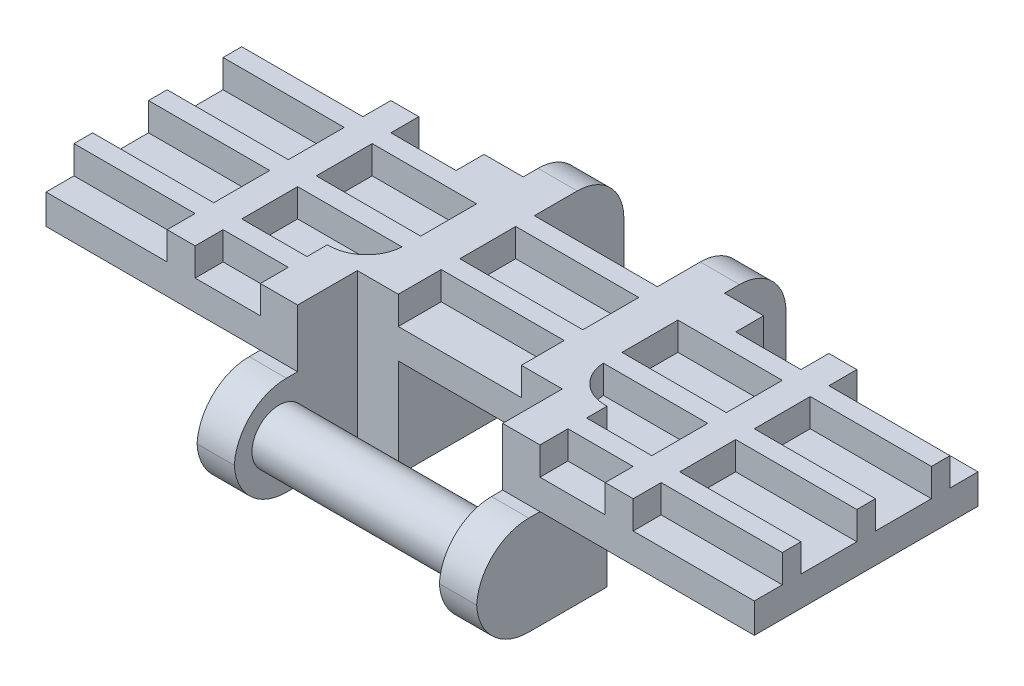
SolidWorks part; units mm, degrees
ref_plane "前视基准面" through (0, 0, 0) normal (0, 0, 1) x (1, 0, 0)
ref_plane "上视基准面" through (0, 0, 0) normal (0, 1, 0) x (1, 0, 0)
ref_plane "右视基准面" through (0, 0, 0) normal (1, 0, 0) x (0, 0, -1)
other "Configuration Table"
sketch "草图1" plane through (0, 0, 0) normal (0, 1, 0) x (1, 0, 0)
  line L1 (-19, -6) -> (19, -6)
  line L2 (-19, -6) -> (-19, 6)
  line L3 (-19, 6) -> (19, 6)
  line L4 (19, -6) -> (19, 6)
  line L5 (-19, -6) -> (19, 6) construction
  line L6 (-19, 6) -> (19, -6) construction
  line L13 (-19, 4.5) -> (19, 4.5)
  line L14 (-19, 4.5) -> (-19, 3.5)
  line L15 (-19, 3.5) -> (19, 3.5)
  line L16 (19, 4.5) -> (19, 3.5)
  line L17 (-19, 0.5) -> (19, 0.5)
  line L18 (-19, 0.5) -> (-19, -0.5)
  line L19 (-19, -0.5) -> (19, -0.5)
  line L20 (19, 0.5) -> (19, -0.5)
  line L21 (-19, -3.5) -> (19, -3.5)
  line L22 (-19, -3.5) -> (-19, -4.5)
  line L23 (-19, -4.5) -> (19, -4.5)
  line L24 (19, -3.5) -> (19, -4.5)
  line L25 (-12.5, 6) -> (-11, 6)
  line L26 (-12.5, 6) -> (-12.5, -6)
  line L27 (-12.5, -6) -> (-11, -6)
  line L28 (-11, 6) -> (-11, -6)
  line L29 (12.5, 6) -> (11, 6)
  line L30 (12.5, 6) -> (12.5, -6)
  line L31 (12.5, -6) -> (11, -6)
  line L32 (11, 6) -> (11, -6)
  point P0 (0, 0)
  point P6 (0, 0)
  dimension "D1" = 38
  dimension "D2" = 12
  dimension "D3" = 11
  dimension "D4" = 11
  dimension "D5" = 1
  dimension "D6" = 1.5
  dimension "D7" = 1.5
  dimension "D8" = 5.5
  dimension "D9" = 1.5
extrude "凸台-拉伸1" add sketch "草图1" along normal blind 1.6 contours L2 L3 L4 L1
extrude "凸台-拉伸2" add sketch "草图1<3>" along normal blind 1.5 from surface contours L13 L16 L15 L14 | L17 L20 L19 L18 | L21 L24 L23 L22 | L26 L27 L28 L25 | L30 L31 L32 L29 starting at face at (0, 1.6, 0)
sketch "草图1<3>" plane through (0, 0, 0) normal (0, 1, 0) x (1, 0, 0) same geometry as "草图1"
sketch "草图2" plane through (0, 0, 0) normal (0, 1, 0) x (1, 0, 0)
  line L0 (0, 0) -> (0, -13.8005) construction
  line L1 (-5.4, 9.3) -> (5.4, 9.3)
  line L2 (-5.4, 9.3) -> (-5.4, -2.8)
  line L3 (-5.4, -2.8) -> (5.4, -2.8)
  line L4 (5.4, 9.3) -> (5.4, -2.8)
  line L5 (-7.5, -2.8) -> (7.5, -2.8)
  line L6 (11, 4.5) -> (-11, 4.5) construction
  line L7 (-7.5, 6) -> (-5.4, 6)
  line L8 (-3.3, 9.3) -> (3.3, 9.3)
  line L9 (-3.3, 9.3) -> (-3.3, -2.8)
  line L10 (-3.3, -2.8) -> (3.3, -2.8)
  line L11 (3.3, 9.3) -> (3.3, -2.8)
  line L16 (-11, -6) -> (11, -6) construction
  line L17 (-11, 6) -> (11, 6) construction
  line L18 (-5.5, -2.4) -> (-5.5, -9.4)
  line L19 (-7.5, -2.4) -> (7.5, -2.4)
  line L20 (-7.5, -2.4) -> (-7.5, -9.4)
  line L21 (-7.5, -9.4) -> (7.5, -9.4)
  line L22 (7.5, -2.4) -> (7.5, -9.4)
  line L23 (5.5, -2.4) -> (5.5, -9.4)
  line L24 (-7.5, 6) -> (-7.5, 4.5)
  line L25 (-7.5, 4.5) -> (-5.4, 4.5)
  line L26 (-5.4, 6) -> (-5.4, 4.5)
  line L27 (7.5, 6) -> (5.4, 6)
  line L28 (7.5, 6) -> (7.5, 4.5)
  line L29 (7.5, 4.5) -> (5.4, 4.5)
  line L30 (5.4, 6) -> (5.4, 4.5)
  point P5 (0, -2.8)
  point P15 (0, 9.3)
  point P20 (0, -9.4)
  dimension "D1" = 10.8
  dimension "D2" = 3.2
  dimension "D3" = 6.6
  dimension "D4" = 3.3
  dimension "D5" = 15
  dimension "D6" = 2
  dimension "D7" = 2
  dimension "D8" = 3.4
  dimension "D9" = 7
extrude "凸台-拉伸3" add sketch "草图2" against normal blind 8.4 from surface contours L1 L11 L3 L4 | L9 L1 L2 L3 | L20 L21 L18 L19 | L19 L23 L21 L22 | L19 L18 L5 L2 | L19 L20 L5 L18 | L19 L2 L3 L9 | L19 L11 L3 L4 | L23 L19 L4 L5 | L19 L23 L5 L22 region at (-4.35, 0, -3.45) region at (4.35, 0, -3.45) region at (-4.35, 0, 2.6) region at (4.35, 0, 2.6) region at (-5.45, 0, 2.6) region at (5.45, 0, 2.6) region at (-6.5, 0, 2.6) region at (6.5, 0, 2.6) region at (-6.5, 0, 6.1) region at (6.5, 0, 6.1) starting at face at (0, 3.1, 0)
extrude "凸台-拉伸5" add sketch "草图2<4>" along normal up to surface (3.1 mm away) contours L27 L30 L29 L28 | L7 L26 L25 L24 up to face at (0, 3.1, -2)
sketch "草图2<4>" plane through (0, 0, 0) normal (0, 1, 0) x (1, 0, 0) same geometry as "草图2"
extrude "切除-拉伸1" cut sketch "草图2<3>" along normal through all contours L0 L5 L3 L18 L21 | L10 L0 L21 L23 L5 L3 region at (2.75, 0, 6.1) region at (-2.75, 0, 6.1)
sketch "草图2<3>" plane through (0, 0, 0) normal (0, 1, 0) x (1, 0, 0) same geometry as "草图2"
fillet "圆角1" radius 3 2 edges at (5.4, -2.65, 2.4) (-5.4, -2.65, 2.4)
sketch "草图3" plane through (-5.5, 0, 0) normal (1, 0, 0) x (0, 0, -1)
  line L2 (-7, -2.5) -> (5.58, -2.5)
  line L3 (2.8, -4.1) -> (9.3, -4.1)
  line L4 (2.8, -4.1) -> (2.8, -5.3)
  line L5 (2.8, -5.3) -> (9.3, -5.3)
  line L6 (9.3, -4.1) -> (9.3, -5.3)
  line L7 (-9.4, -5.3) -> (-9.4, 3.1) construction
  line L8 (-6, 3.1) -> (-9.4, 3.1)
  line L9 (-6, 3.1) -> (-6, 0)
  line L10 (-6, 0) -> (-9.4, 0)
  line L11 (-9.4, 3.1) -> (-9.4, 0)
  circle A0 centre (-7, -2.5) radius 1.45
  circle A1 centre (5.58, -2.5) radius 1.7
  dimension "D1" = 2.9
  dimension "D3" = 3.4
  dimension "D7" = 7
  dimension "D2" = 2.5
  dimension "D4" = 1.2
  dimension "D5" = 6.5
  dimension "D6" = 12.58
extrude "凸台-拉伸4" add sketch "草图3" along normal up to next contours A0
extrude "切除-拉伸2" cut sketch "草图3<3>" along normal through all both and the other way through all contours L3 L6 L5 L4 | A1 | L11 L10 L9 L8
sketch "草图3<3>" plane through (-5.5, 0, 0) normal (1, 0, 0) x (0, 0, -1) same geometry as "草图3"
fillet "圆角2" radius 2.8 4 edges at (6.5, -5.3, 9.4) (-6.5, -5.3, 9.4) (-6.5, 0, 9.4) (6.5, 0, 9.4)
fillet "圆角3" radius 2.5 2 edges at (-4.35, 3.1, -9.3) (4.35, 3.1, -9.3)
fillet "圆角4" radius 1 2 edges at (-4.35, -4.1, -9.3) (4.35, -4.1, -9.3)
fillet "圆角5" radius 0.3 4 edges at (-4.35, -4.1, -6.1545) (4.35, -4.1, -6.1545) (4.35, -4.1, -5.0055) (-4.35, -4.1, -5.0055)
fillet "圆角6" radius 2 2 edges at (5.4, 2.35, 2.4) (-5.4, 2.35, 2.4)
